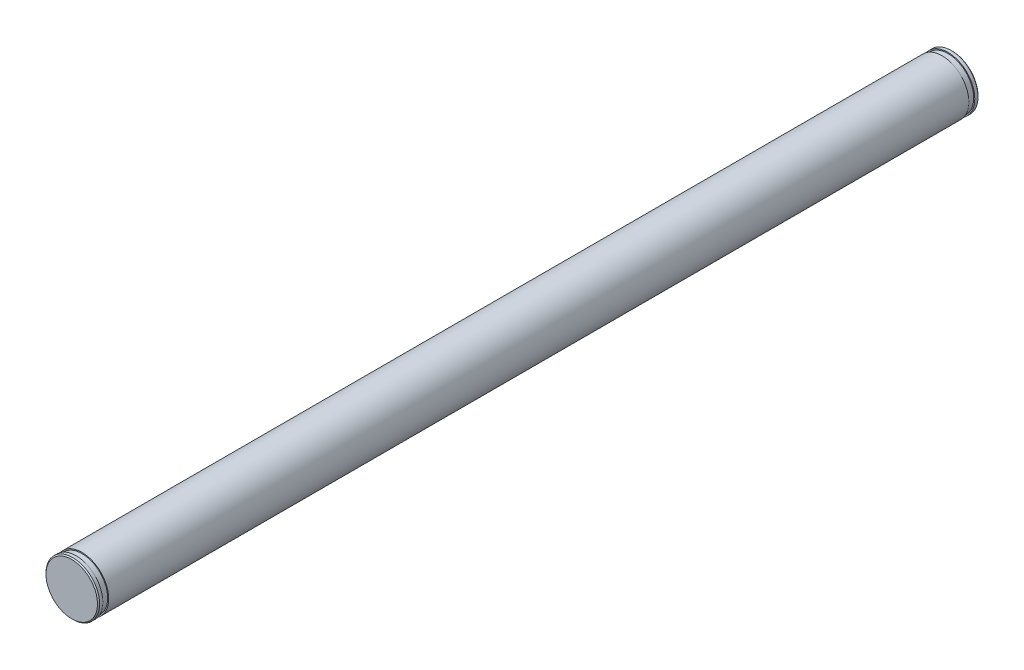
SolidWorks part; units mm, degrees
ref_plane "Vorne" through (0, 0, 0) normal (0, 0, 1) x (1, 0, 0)
ref_plane "Oben" through (0, 0, 0) normal (0, 1, 0) x (1, 0, 0)
ref_plane "Seite" through (0, 0, 0) normal (1, 0, 0) x (0, 0, -1)
sketch "Skizze1" plane through (0, 0, 0) normal (0, 0, 1) x (1, 0, 0)
  circle A0 centre (0, 0) radius 5
  dimension "D1" = 10
sketch "Skizze7" plane through (0, 0, 0) normal (1, 0, 0) x (0, 0, -1)
  line L0 (-163.4, 5) -> (-163.4, 4.8)
  line L1 (50, 0) -> (-50, 0) construction
  line L2 (-163.4, 4.8) -> (-162.3, 4.8)
  line L3 (-162.3, 4.8) -> (-162.3, 5)
  line L5 (-1.9, 5) -> (-1.9, 4.8)
  line L6 (-1.9, 4.8) -> (-0.8, 4.8)
  line L7 (-0.8, 4.8) -> (-0.8, 5)
  line L10 (-164.2, 0) -> (0, 0)
  line L11 (0, 50) -> (0, -50) construction
  line L12 (-162.3, 5) -> (-1.9, 5)
  line L13 (-163.4, 5) -> (-164.2, 5)
  line L14 (-164.2, 5) -> (-164.2, 0)
  line L16 (0, 0) -> (0, 5)
  line L17 (0, 5) -> (-0.8, 5)
  dimension "D1" = 0.2
  dimension "D2" = 1.1
  dimension "D4" = 160.4
  dimension "D5" = 0.8
  dimension "D3" = 4.8
revolve "Rotation1" add sketch "Skizze7" angle 360 about L10
chamfer "Fase1" distance 0.2 angle 45 2 edges at (5, 0, 0) (5, 0, 164.2)
equation "\"d1\"= 10mm"
equation "\"D1@Skizze1\"= \"d1\""
equation "\"n\"= 0.6mm"
equation "\"m\"= 1.1mm"
equation "\"d2\"= 9.6mm"
equation "\"D2@Skizze7\"= \"m\""
equation "\"D1@Skizze7\" = ( \"d1\" - \"d2\" ) / 2"
